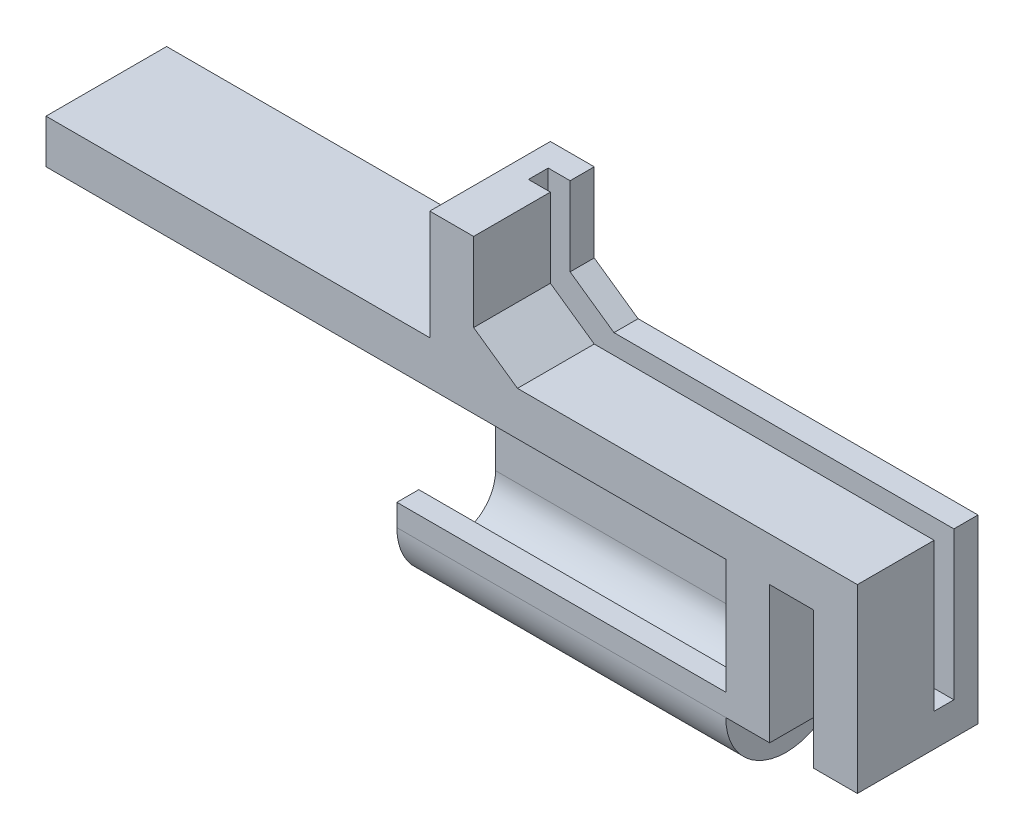
SolidWorks part; units mm, degrees
note: The reader was unsure of these and kept them because the rebuilt part matched: shared geometry of "Sketch1<3>", "Sketch1<4>", "Sketch1<6>".
ref_plane "Front Plane" through (0, 0, 0) normal (0, 0, 1) x (1, 0, 0)
ref_plane "Top Plane" through (0, 0, 0) normal (0, 1, 0) x (1, 0, 0)
ref_plane "Right Plane" through (0, 0, 0) normal (1, 0, 0) x (0, 0, -1)
sketch "Sketch1" plane through (0, 0, 0) normal (1, 0, 0) x (0, 0, -1)
  line L0 (0, 0) -> (0, 8.25)
  line L1 (0, 0) -> (5.5, 0)
  line L2 (0, 8.25) -> (-10, 8.25)
  line L3 (0, 6.25) -> (5.5, 6.25)
  line L4 (5.5, 8.25) -> (0, 8.25)
  line L5 (5.5, 8.25) -> (5.5, 6.25)
  line L6 (5.5, 6.25) -> (5.5, 0)
  line L7 (1, 0) -> (1, 8.25)
  line L8 (4.5, 0) -> (4.5, 8.25)
  line L9 (4.5, 1) -> (5.5, 1)
  line L10 (1, 1) -> (0, 1)
  arc A0 (0, 0) -> (5.5, 0) centre (2.75, 0) ccw
  arc A1 (1, 0) -> (4.5, 0) centre (2.75, 0) ccw
  dimension "D6" = 1
  dimension "D1" = 5.5
  dimension "D2" = 8.25
  dimension "D3" = 10
  dimension "D4" = 2
  dimension "D5" = 5.5
  dimension "D7" = 1
extrude "Boss-Extrude1" add sketch "Sketch1" along normal blind 37 contours L5 L4 L0 L3 | L3 L7 L4 L0 | L8 L3 L5 L4
extrude "Boss-Extrude2" add sketch "Sketch1<3>" along normal blind 2 from offset 35 contours L6 L3 L0 L1 | L8 L1 L6 L3 | L1 L7 L3 L0 | L7 L10 L0 L1 | L9 L8 L1 L6
sketch "Sketch1<3>" plane through (0, 0, 0) normal (1, 0, 0) x (0, 0, -1) same geometry as "Sketch1"
extrude "Boss-Extrude3" add sketch "Sketch1<4>" along normal blind 2 from offset 31 contours L6 L3 L0 L1 | L8 L1 L6 L3 | L1 L7 L3 L0 | L7 L10 L0 L1 | L9 L8 L1 L6
sketch "Sketch1<4>" plane through (0, 0, 0) normal (1, 0, 0) x (0, 0, -1) same geometry as "Sketch1"
extrude "Boss-Extrude5" add sketch "Sketch1<6>" along normal blind 15 from offset 16 contours L8 L1 L6 L3 | A1 L1 A0 | L9 L8 L1 L6 | L7 L10 L0 L1
sketch "Sketch1<6>" plane through (0, 0, 0) normal (1, 0, 0) x (0, 0, -1) same geometry as "Sketch1"
sketch "Sketch2" plane through (0, 8.25, 0) normal (0, 1, 0) x (1, 0, 0)
  line L0 (33.5, 5.5) -> (33.5, 0) construction
  line L1 (37, 5.5) -> (0, 5.5) construction
  line L2 (37, 0) -> (0, 0) construction
  line L3 (37, 5.5) -> (37, 0) construction
  line L4 (19.5, 5.5) -> (19.5, 0) construction
  line L5 (19.5, 5.5) -> (17.5, 5.5)
  line L6 (17.5, 5.5) -> (17.5, 0)
  line L7 (17.5, 0) -> (19.5, 0)
  line L8 (19.5, 0) -> (19.5, 5.5)
  point P6 (37, 2.75)
  dimension "D1" = 3.5
  dimension "D2" = 14
  dimension "D3" = 2
extrude "Boss-Extrude6" add sketch "Sketch2" along normal blind 5
sketch "Sketch3" plane through (37, 0, 0) normal (1, 0, 0) x (0, 0, -1)
  line L0 (4.4, 13.66) -> (4.4, 1.5)
  line L1 (0, 0) -> (5.5, 0) construction
  line L2 (4.4, 1.5) -> (3.5, 1.5)
  line L3 (3.5, 1.5) -> (3.5, 13.66)
  line L4 (3.5, 13.66) -> (4.4, 13.66)
  line L5 (0, 0) -> (0, 8.25) construction
  dimension "D1" = 0.9
  dimension "D2" = 3.5
  dimension "D3" = 1.5
extrude "Cut-Extrude1" cut sketch "Sketch3" against normal blind 18.5
chamfer "Chamfer1" distance 2 angle 35 1 edges at (31, 1.5, -3.95)
chamfer "Chamfer2" distance 2 angle 35 2 edges
